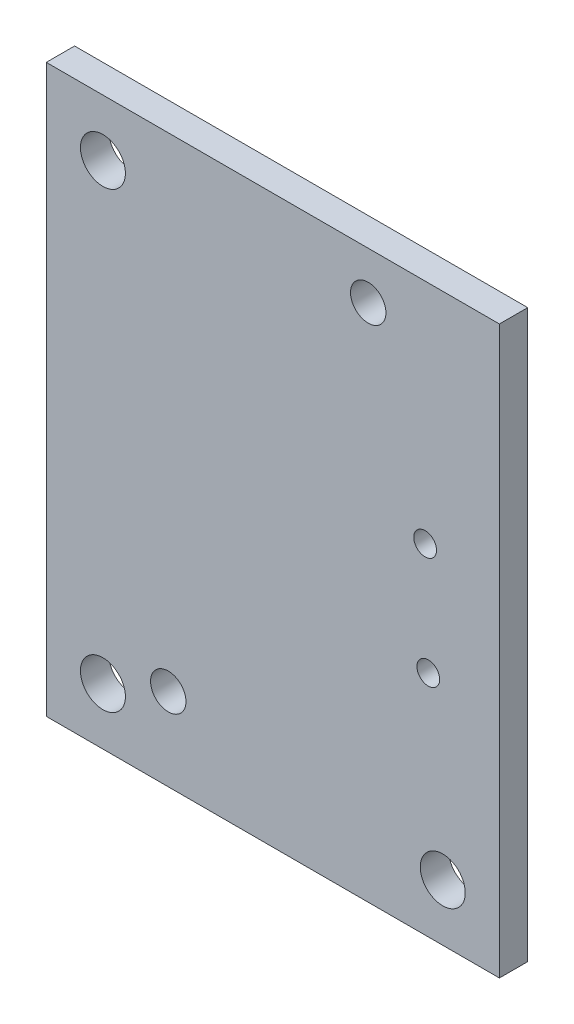
SolidWorks part; units mm, degrees
ref_plane "Front Plane" through (0, 0, 0) normal (1, 0, 0) x (0, 1, 0)
ref_plane "Top Plane" through (0, 0, 0) normal (0, 0, 1) x (0, 1, 0)
ref_plane "Right Plane" through (0, 0, 0) normal (0, 1, 0) x (-1, 0, 0)
sketch "Sketch2" plane through (0, 0, 0) normal (0, 0, 1) x (0, 1, 0)
  line L1 (0, 0) -> (127, 0)
  line L2 (0, 0) -> (0, 101.6)
  line L3 (0, 101.6) -> (127, 101.6)
  line L4 (127, 0) -> (127, 101.6)
  line L5 (12.7, 88.9) -> (114.3, 88.9) construction
  line L6 (12.7, 88.9) -> (12.7, 12.7) construction
  line L7 (12.7, 12.7) -> (114.3, 12.7) construction
  line L8 (114.3, 88.9) -> (114.3, 12.7) construction
  line L9 (12.7, 12.7) -> (73.436, 12.7) construction
  line L10 (12.7, 12.7) -> (12.7, 24.2176) construction
  line L11 (12.7, 24.2176) -> (73.436, 24.2176) construction
  line L12 (73.436, 12.7) -> (73.436, 24.2176) construction
  line L13 (12.7, 12.7) -> (88.9, 12.7) construction
  line L14 (12.7, 12.7) -> (12.7, 20.1554) construction
  line L15 (12.7, 20.1554) -> (88.9, 20.1554) construction
  line L16 (88.9, 12.7) -> (88.9, 20.1554) construction
  dimension "D1" = 12.7
  dimension "D2" = 12.7
  dimension "D3" = 12.7
  dimension "D4" = 12.7
  dimension "D5" = 127
  dimension "D6" = 101.6
  dimension "D7" = 11.5176
  dimension "D8" = 60.736
  dimension "D9" = 7.4554
  dimension "D10" = 76.2
extrude "Boss-Extrude1" add sketch "Sketch2" along normal blind 6.35
hole_wizard "3/8 Clearance Hole1" positions "Sketch3" profile "Sketch4" hole size "3/8" standard "ANSI Inch" end condition through all
sketch "Sketch3" plane through (0, 0, 6.35) normal (0, 0, 1) x (1, 0, 0)
  point P0 (-12.7, 12.7)
  point P3 (-88.9, 12.7)
  point P6 (-88.9, 114.3)
sketch "Sketch4" plane through (-12.7, 12.7, 6.35) normal (1, 0, 0) x (0, -1, 0)
  line L0 (0, 0) -> (0, 6.35)
  line L1 (0, 6.35) -> (5.0419, 6.35)
  line L2 (5.0419, 6.35) -> (5.0419, 0)
  line L5 (5.0419, 0) -> (0, 0)
  line L11 (0, -6.35) -> (0, 107.95) construction
  dimension "Thru Hole Dia." = 10.0838
  dimension "Thru Hole Depth" = 6.35
hole_wizard "Tap Drill for 1/4-20 Tap1" positions "Sketch7" profile "Sketch6" hole size "1/4-20" standard "ANSI Inch" end condition through all
sketch "Sketch7" plane through (0, 0, 6.35) normal (0, 0, 1) x (1, 0, 0)
  circle A0 centre (-15.9447, 51.261) radius 186.6805 construction
  circle A3 centre (-16.6512, 75.9912) radius 189.0164 construction
  point P0 (-15.9447, 51.261)
  point P3 (-16.6512, 75.9912)
  point P6 (0, 0)
  point P9 (0, 0)
sketch "Sketch6" plane through (-15.9447, 51.261, 6.35) normal (1, 0, 0) x (0, -1, 0)
  line L0 (0, 0) -> (0, 6.35)
  line L1 (0, 6.35) -> (2.5527, 6.35)
  line L2 (2.5527, 6.35) -> (2.5527, 0)
  line L5 (2.5527, 0) -> (0, 0)
  line L11 (0, -6.35) -> (0, 107.95) construction
  dimension "Thru Hole Dia." = 5.1054
  dimension "Thru Hole Depth" = 6.35
sketch "Sketch8" plane through (0, 0, 6.35) normal (0, 0, 1) x (1, 0, 0)
  line L0 (-15.9447, 51.261) -> (-101.6, -26.6247) construction
  line L1 (-16.6512, 75.9912) -> (-57.0224, 127) construction
  line L2 (0, 0) -> (0, 127) construction
  line L3 (-101.6, 127) -> (-101.6, 0) construction
  line L6 (0, 127) -> (-101.6, 127) construction
  line L7 (-65.3083, 6.375) -> (-74.2503, 18.5194) construction
  line L8 (-41.2408, 107.0601) -> (-29.4152, 116.4195) construction
  dimension "D1" = 38.36
  dimension "D2" = 47.72
  dimension "D3" = 15.0812
  dimension "D4" = 15.0812
hole_wizard "Tap Drill for 3/8-16 Tap2" positions "Sketch9" profile "Sketch10" hole size "3/8-16" standard "ANSI Inch"
sketch "Sketch9" plane through (0, 0, 6.35) normal (0, 0, 1) x (1, 0, 0)
  point P0 (-74.2503, 18.5194)
  point P3 (-29.4152, 116.4195)
sketch "Sketch10" plane through (-74.2503, 18.5194, 6.35) normal (1, 0, 0) x (0, -1, 0)
  line L0 (0, 0) -> (0, 15.0847)
  line L1 (0, 15.0847) -> (3.9687, 12.7)
  line L2 (3.9687, 12.7) -> (3.9687, 0)
  line L5 (3.9687, 0) -> (0, 0)
  line L10 (0, 15.0847) -> (-3.9688, 12.7) construction
  line L11 (0, -6.35) -> (0, 107.95) construction
  dimension "Hole Dia." = 7.9375
  dimension "Hole Depth" = 12.7
  dimension "Drill Angle" = 118
